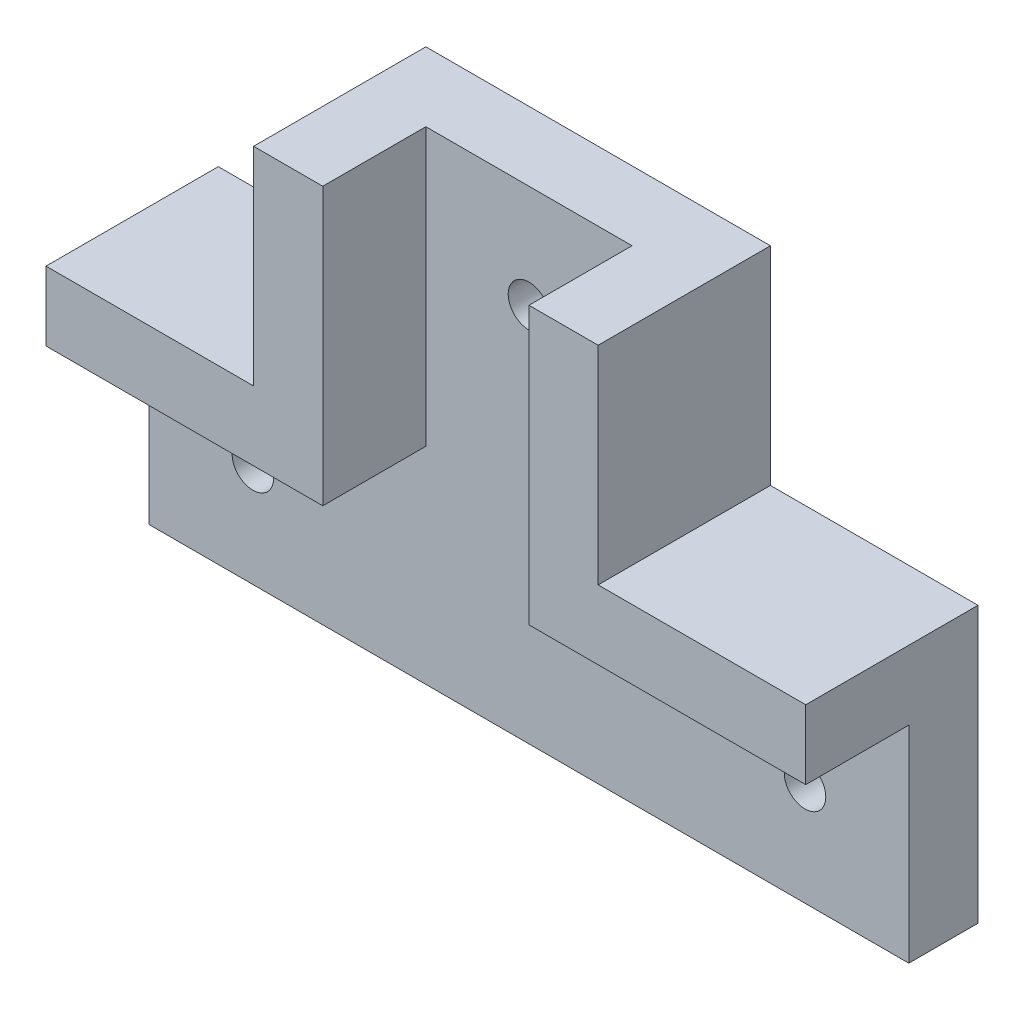
SolidWorks part; units mm, degrees
ref_plane "Front Plane" through (0, 0, 0) normal (0, 0, 1) x (1, 0, 0)
ref_plane "Top Plane" through (0, 0, 0) normal (0, 1, 0) x (1, 0, 0)
ref_plane "Right Plane" through (0, 0, 0) normal (1, 0, 0) x (0, 0, -1)
sketch "Sketch1" plane through (0, 0, 0) normal (0, 0, 1) x (1, 0, 0)
  line L0 (14.2137, -4.2647) -> (34.2137, -4.2647)
  line L1 (-20.6863, -4.2647) -> (-0.6863, -4.2647)
  line L2 (-20.6863, -4.2647) -> (-20.6863, -19.1647)
  line L3 (-20.6863, -19.1647) -> (34.2137, -19.1647)
  line L4 (34.2137, -4.2647) -> (34.2137, -19.1647)
  line L5 (-0.6863, 15.7353) -> (14.2137, 15.7353)
  line L6 (-0.6863, 15.7353) -> (-0.6863, -4.2647)
  line L8 (14.2137, 15.7353) -> (14.2137, -4.2647)
  dimension "D1" = 14.9
  dimension "D2" = 20
  dimension "D3" = 20
  dimension "D4" = 14.9
  dimension "D5" = 20
extrude "Boss-Extrude1" add sketch "Sketch1" along normal blind 5
sketch "Sketch2" plane through (0, 0, 0) normal (0, 0, -1) x (-1, 0, 0)
  line L0 (0.6863, 15.7353) -> (5.6863, 15.7353)
  line L1 (5.6863, 15.7353) -> (5.6863, 0.7353)
  line L2 (20.6863, -4.2647) -> (20.6863, 0.7353)
  line L3 (20.6863, 0.7353) -> (6.08, 0.7353)
  line L4 (20.6863, -4.2647) -> (0.6863, -4.2647)
  line L5 (0.6863, 15.7353) -> (0.6863, -4.2647)
  line L6 (6.08, 0.7353) -> (5.6863, 0.7353)
  dimension "D1" = 5
  dimension "D2" = 5
extrude "Boss-Extrude2" add sketch "Sketch2" against normal blind 12.45 contours L3 L6 L1 L0 L5 L4 L2
sketch "Sketch4" plane through (0, 0, 0) normal (0, 0, -1) x (-1, 0, 0)
  line L0 (20.6863, -19.1647) -> (-34.2137, -19.1647)
  line L1 (-34.2137, -19.1647) -> (-34.2137, -24.1647)
  line L2 (-34.2137, -24.1647) -> (20.6863, -24.1647)
  line L3 (20.6863, -24.1647) -> (20.6863, -19.1647)
  dimension "D1" = 5
ref_plane "Plane4" through (6.7637, 0, 0) normal (-1, 0, 0) x (0, 0, 1)
ref_plane "Plane5" through (-5.7363, 0, 0) normal (-1, 0, 0) x (0, 0, 1)
mirror "Mirror1" about plane through (6.7637, 0, 0) normal (-1, 0, 0) of "Boss-Extrude2"
sketch "Sketch6" plane through (0, 0, 5) normal (0, 0, 1) x (1, 0, 0)
  line L0 (6.7637, 6.8475) -> (6.7637, -6.8475) construction
  line L1 (-20.6863, -4.2647) -> (-20.6863, -19.1647) construction
  line L2 (-20.6863, -4.2647) -> (-0.6863, -4.2647) construction
  line L3 (34.2137, -4.2647) -> (14.2137, -4.2647) construction
  line L5 (34.2137, -19.1647) -> (34.2137, -4.2647) construction
  line L6 (14.2137, 15.7353) -> (-0.6863, 15.7353) construction
  circle A0 centre (6.7637, 8.2353) radius 1.5
  circle A1 centre (-13.1863, -11.7647) radius 1.5
  circle A2 centre (26.7137, -11.7647) radius 1.5
  dimension "D1" = 3
  dimension "D2" = 3
  dimension "D3" = 3
  dimension "D5" = 7.5
  dimension "D7" = 7.5
  dimension "D8" = 7.5
  dimension "D4" = 7.5
  dimension "D6" = 7.5
ref_plane "Plane6" through (-5.6863, 0.7353, 12.45) normal (0, -1, 0) x (-1, 0, 0)
extrude "Cut-Extrude3" cut sketch "Sketch6" against normal through all
